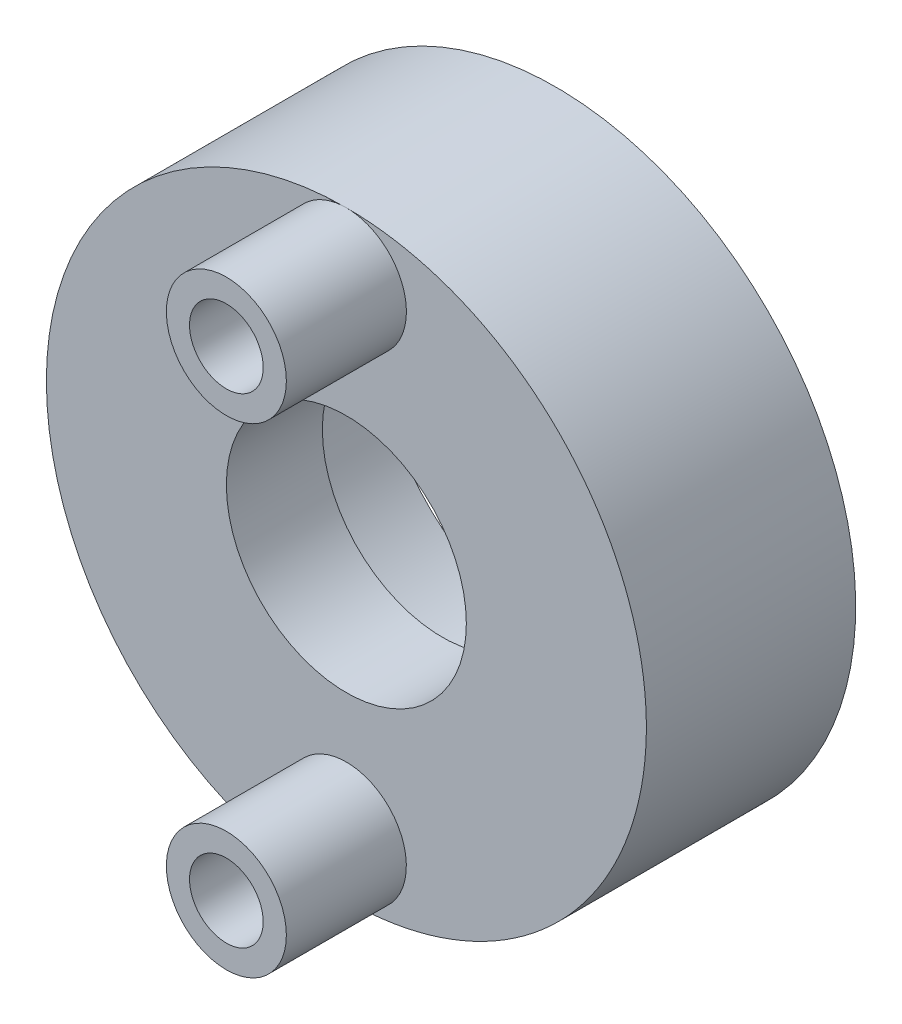
SolidWorks part; units mm, degrees
ref_plane "Front Plane" through (0, 0, 0) normal (0, 0, 1) x (1, 0, 0)
ref_plane "Top Plane" through (0, 0, 0) normal (0, 1, 0) x (1, 0, 0)
ref_plane "Right Plane" through (0, 0, 0) normal (1, 0, 0) x (0, 0, -1)
sketch "Sketch1" plane through (0, 0, 0) normal (0, 0, 1) x (1, 0, 0)
  line L0 (0, 0) -> (9.3823, 0) construction
  circle A0 centre (0, 0) radius 15.875
  circle A1 centre (0, 12.7) radius 1.95
  circle A2 centre (0, -12.7) radius 1.95
  circle A3 centre (0, 12.7) radius 3.175
  circle A4 centre (0, -12.7) radius 3.175
  circle A5 centre (0, 0) radius 6.35
  dimension "D1" = 31.75
  dimension "D2" = 3.9
  dimension "D4" = 12.7
  dimension "D3" = 12.7
extrude "Boss-Extrude1" add sketch "Sketch1" against normal blind 5.08 contours A0 A4 A3 A5 | A3 A1 | A4 A2 region at (2.1816, 14.8816, 0) region at (-2.1816, -10.5184, 0) region at (10.9078, -10.9078, 0)
extrude "Boss-Extrude2" add sketch "Sketch1<3>" along normal blind 6.35 contours A3 A1 | A4 A2 region at (2.1816, 14.8816, 0) region at (-2.1816, -10.5184, 0)
sketch "Sketch1<3>" plane through (0, 0, 0) normal (0, 0, 1) x (1, 0, 0) same geometry as "Sketch1"
sketch "Sketch2" plane through (0, 0, -5.08) normal (0, 0, -1) x (-1, 0, 0)
  circle A0 centre (0, 0) radius 9.5
  circle A1 centre (0, 0) radius 15.875
  circle A2 centre (0, 0) radius 15.875
  dimension "D2" = 19
  dimension "D1" = 0
extrude "Boss-Extrude3" add sketch "Sketch2" along normal blind 6
